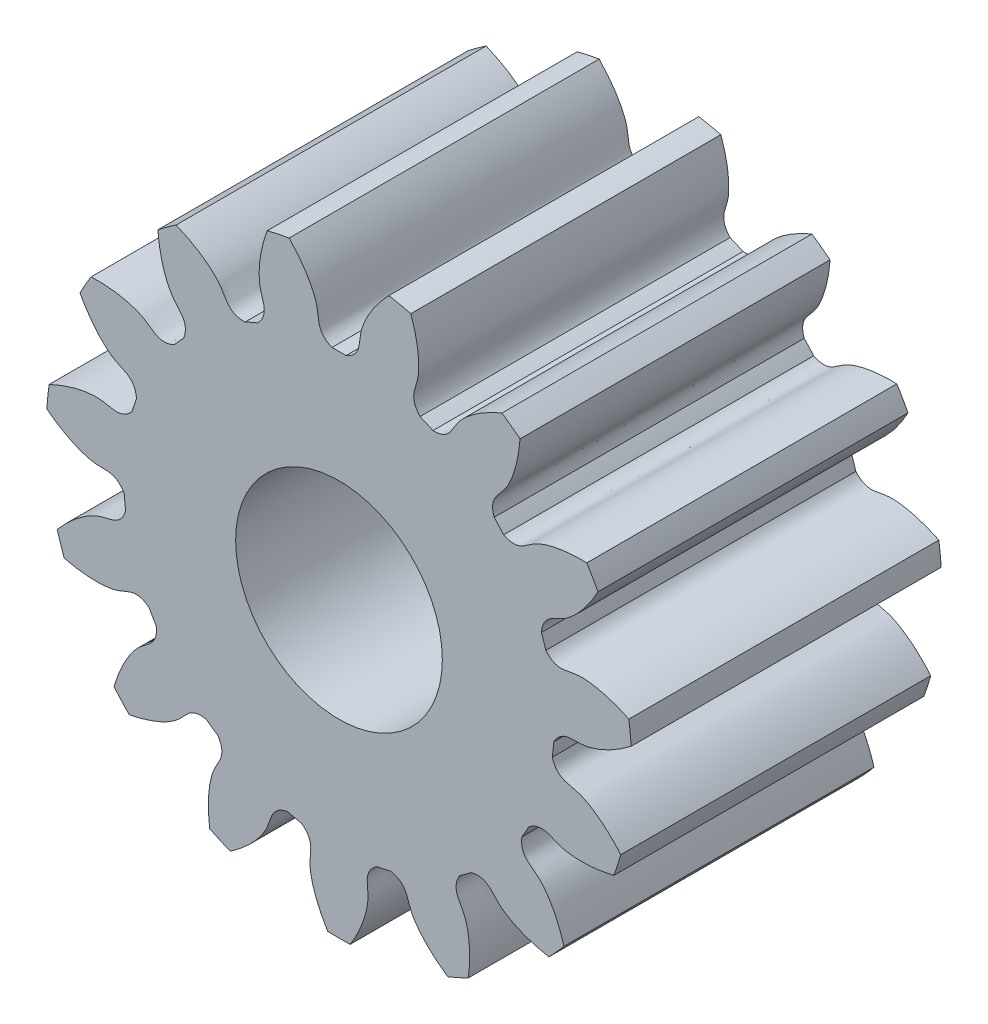
SolidWorks part; units mm, degrees
ref_plane "前视基准面" through (0, 0, 0) normal (0, 0, 1) x (1, 0, 0)
ref_plane "上视基准面" through (0, 0, 0) normal (0, 1, 0) x (1, 0, 0)
ref_plane "右视基准面" through (0, 0, 0) normal (1, 0, 0) x (0, 0, -1)
sketch "草图1" plane through (0, 0, 0) normal (0, 0, 1) x (1, 0, 0)
  circle A0 centre (0, 0) radius 4.25
extrude "凸台-拉伸1" add sketch "草图1" along normal blind 4.5
ref_axis "基准轴1" through (0, 0, 4.5) along (0, 0, -1)
sketch "草图2" plane through (0, 0, 0) normal (0, 0, 1) x (1, 0, 0)
  line L0 (0, 0) -> (0, 4.25) construction
  circle A0 centre (0, 0) radius 4.25 construction
  arc A1 (0.1021, 3.1233) -> (-0.1021, 3.1233) centre (0, 0) ccw
  arc A2 (1.6234, 4.818) -> (-1.6234, 4.818) centre (0, 0) ccw
  spline S0 degree 3 poles (0.1021, 3.1233) (0.3286, 3.2172) (0.2861, 3.3932) (0.3256, 3.5543) (0.3287, 3.5658) (0.3324, 3.5787) (0.3368, 3.5928) (0.3419, 3.6082) (0.3478, 3.6248) (0.3545, 3.6426) (0.3621, 3.6616) (0.3706, 3.6817) (0.3801, 3.703) (0.3906, 3.7253) (0.4022, 3.7486) (0.4149, 3.773) (0.4288, 3.7984) (0.4438, 3.8247) (0.4601, 3.8519) (0.4777, 3.8799) (0.4967, 3.9088) (0.517, 3.9385) (0.5387, 3.9689) (0.5618, 4) (0.5865, 4.0317) (0.6126, 4.064) (0.6403, 4.0969) (0.6696, 4.1303) (0.7005, 4.1641) (0.733, 4.1983) (0.7673, 4.2329) (0.8032, 4.2678) (0.8408, 4.3029) (0.8801, 4.3381) (0.9213, 4.3735) (0.9642, 4.409) (1.0089, 4.4445) (1.0555, 4.4799) (1.1039, 4.5153) (1.1541, 4.5504) (1.2062, 4.5854) (1.2602, 4.62) (1.316, 4.6543) (1.3738, 4.6882) (1.4334, 4.7216) (1.5163, 4.7659) (1.5801, 4.7975) (1.6234, 4.818) knots 0 0 0 0 0.202473 0.206979 0.212085 0.217793 0.224101 0.23101 0.23852 0.24663 0.255341 0.264653 0.274566 0.285079 0.296194 0.307909 0.320225 0.333141 0.346659 0.360777 0.375496 0.390816 0.406736 0.423257 0.440379 0.458102 0.476426 0.49535 0.514875 0.535001 0.555728 0.577055 0.598984 0.621513 0.644642 0.668373 0.692704 0.717636 0.743169 0.769303 0.796037 0.823373 0.851309 0.879845 0.908983 0.938721 1 1 1 1
  spline S1 degree 3 poles (-0.1021, 3.1233) (-0.3286, 3.2172) (-0.2861, 3.3932) (-0.3256, 3.5543) (-0.3287, 3.5658) (-0.3324, 3.5787) (-0.3368, 3.5928) (-0.3419, 3.6082) (-0.3478, 3.6248) (-0.3545, 3.6426) (-0.3621, 3.6616) (-0.3706, 3.6817) (-0.3801, 3.703) (-0.3906, 3.7253) (-0.4022, 3.7486) (-0.4149, 3.773) (-0.4288, 3.7984) (-0.4438, 3.8247) (-0.4601, 3.8519) (-0.4777, 3.8799) (-0.4967, 3.9088) (-0.517, 3.9385) (-0.5387, 3.9689) (-0.5618, 4) (-0.5865, 4.0317) (-0.6126, 4.064) (-0.6403, 4.0969) (-0.6696, 4.1303) (-0.7005, 4.1641) (-0.733, 4.1983) (-0.7673, 4.2329) (-0.8032, 4.2678) (-0.8408, 4.3029) (-0.8801, 4.3381) (-0.9213, 4.3735) (-0.9642, 4.409) (-1.0089, 4.4445) (-1.0555, 4.4799) (-1.1039, 4.5153) (-1.1541, 4.5504) (-1.2062, 4.5854) (-1.2602, 4.62) (-1.316, 4.6543) (-1.3738, 4.6882) (-1.4334, 4.7216) (-1.5163, 4.7659) (-1.5801, 4.7975) (-1.6234, 4.818) knots 0 0 0 0 0.202473 0.206979 0.212085 0.217793 0.224101 0.23101 0.23852 0.24663 0.255341 0.264653 0.274566 0.285079 0.296194 0.307909 0.320225 0.333141 0.346659 0.360777 0.375496 0.390816 0.406736 0.423257 0.440379 0.458102 0.476426 0.49535 0.514875 0.535001 0.555728 0.577055 0.598984 0.621513 0.644642 0.668373 0.692704 0.717636 0.743169 0.769303 0.796037 0.823373 0.851309 0.879845 0.908983 0.938721 1 1 1 1
extrude "切除-拉伸1" cut sketch "草图2" along normal through all
pattern_circular "阵列(圆周)1" count 15 every 24 about axis through (0, 0, 4.5) along (0, 0, -1) of "切除-拉伸1"
sketch "草图3" plane through (0, 0, 0) normal (0, 0, 1) x (1, 0, 0)
  circle A0 centre (0, 0) radius 3.75 construction
  dimension "Dn" = 7.5
sketch "草图4" plane through (0, 0, 4.5) normal (0, 0, 1) x (1, 0, 0)
  circle A0 centre (0, 0) radius 1.5
  dimension "D1" = 3
extrude "切除-拉伸2" cut sketch "草图4" against normal up to next
